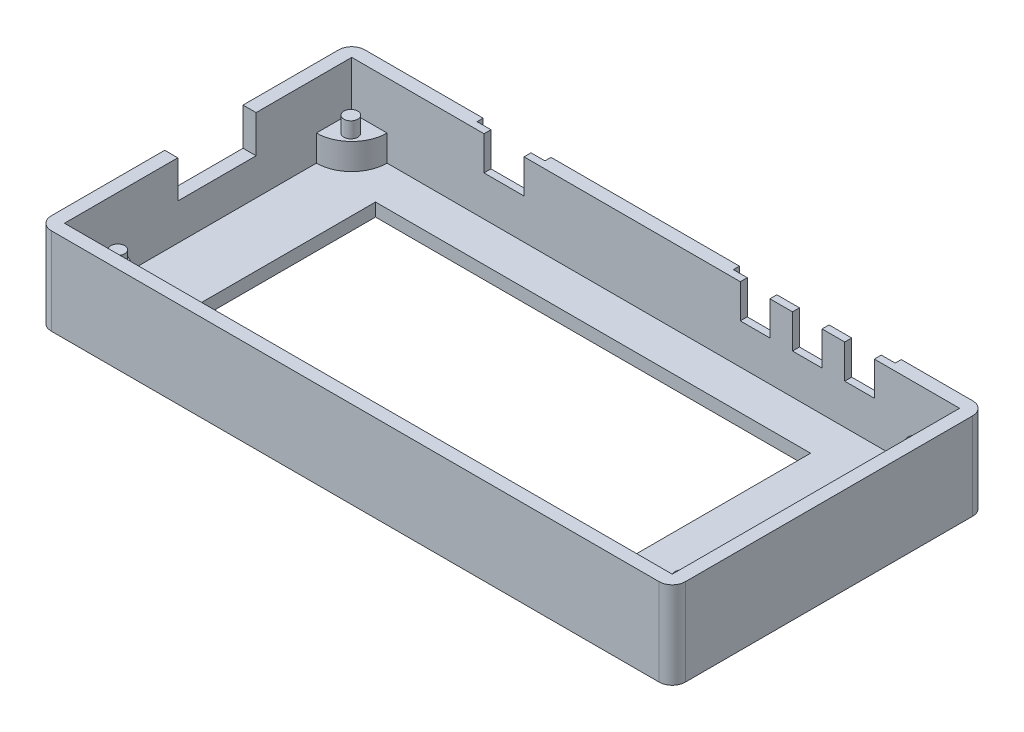
SolidWorks part; units mm, degrees
ref_plane "前视基准面" through (0, 0, 0) normal (0, 0, 1) x (1, 0, 0)
ref_plane "上视基准面" through (0, 0, 0) normal (0, 1, 0) x (1, 0, 0)
ref_plane "右视基准面" through (0, 0, 0) normal (1, 0, 0) x (0, 0, -1)
sketch "草图1" plane through (0, 0, 0) normal (0, 1, 0) x (1, 0, 0)
  line L1 (-34.9275, 15.494) -> (34.9275, 15.494)
  line L2 (-34.9275, 15.494) -> (-34.9275, -15.494)
  line L4 (34.9275, 15.494) -> (34.9275, -15.494)
  line L5 (-34.9275, 15.494) -> (34.9275, -15.494) construction
  line L6 (-34.9275, -15.494) -> (34.9275, 15.494) construction
  line L8 (-34.9275, -15.494) -> (-34.9275, -17.526)
  line L9 (-34.9275, -17.526) -> (34.9275, -17.526)
  line L10 (34.9275, -15.494) -> (34.9275, -17.526)
  line L11 (-34.9275, -15.494) -> (34.9275, -15.494)
  line L12 (-30.8635, -17.526) -> (-30.8635, 15.494) construction
  line L13 (29.7365, 15.494) -> (29.7365, -17.526) construction
  line L14 (-27.6635, 10.962) -> (-27.6635, -13.994)
  line L15 (22.3365, 10.962) -> (22.3365, -13.994)
  line L16 (0, 15.494) -> (0, -15.494) construction
  line L17 (-34.9275, 0) -> (34.9275, 0) construction
  line L18 (-27.6635, 10.962) -> (22.3365, 10.962)
  line L19 (-27.6635, -13.994) -> (22.3365, -13.994)
  arc A0 (-34.9275, -11.43) -> (-31.408, -17.526) centre (-34.9275, -15.494) cw
  arc A1 (-34.9275, 11.43) -> (-30.8635, 15.494) centre (-34.9275, 15.494) ccw
  arc A3 (34.9275, -10.43) -> (30.2891, -17.526) centre (34.9275, -15.494) ccw
  arc A4 (34.9275, 10.43) -> (29.8635, 15.494) centre (34.9275, 15.494) cw
  point P0 (0, 0)
  dimension "D4" = 4.064
  dimension "D5" = 4.064
  dimension "D6" = 5.064
  dimension "D1" = 30.988
  dimension "D2" = 69.855
  dimension "D3" = 2.032
  dimension "D7" = 5.191
  dimension "D8" = 3.2
  dimension "D9" = 7.4
  dimension "D10" = 4.532
  dimension "D11" = 3.532
extrude "凸台-拉伸1" add sketch "草图1" along normal blind 1.5 contours L8 L9 L10 L4 L1 L2
extrude "切除-拉伸2" cut sketch "草图1<6>" along normal up to next contours L14 L19 L15 L18
sketch "草图1<6>" plane through (0, 0, 0) normal (0, 1, 0) x (1, 0, 0) same geometry as "草图1"
extrude "拉伸-薄壁1" add sketch "草图1<7>" along normal blind 10 separate body thin contours L4 L10 L9 L8 L2 L1 thin type one direction wall 1.5
sketch "草图1<7>" plane through (0, 0, 0) normal (0, 1, 0) x (1, 0, 0) same geometry as "草图1"
fillet "圆角1" radius 1.5 4 edges at (36.4275, 5, -16.994) (36.4275, 5, 19.026) (-36.4275, 5, 19.026) (-36.4275, 5, -16.994)
sketch "草图2" plane through (0, 1.5, 0) normal (0, 1, 0) x (1, 0, 0)
  line L2 (-34.9275, -11.43) -> (-34.9275, -17.526)
  line L3 (-34.9275, -17.526) -> (-31.408, -17.526)
  line L4 (-30.8635, 15.494) -> (-34.9275, 15.494)
  line L5 (-34.9275, 15.494) -> (-34.9275, 11.43)
  line L7 (29.8635, 15.494) -> (34.9275, 15.494)
  line L8 (34.9275, 15.494) -> (34.9275, 10.43)
  line L9 (34.9275, -10.43) -> (34.9275, -17.526)
  line L10 (34.9275, -17.526) -> (30.2891, -17.526)
  arc A0 (29.8635, 15.494) -> (34.9275, 10.43) centre (34.9275, 15.494) ccw construction
  arc A1 (34.9275, -10.43) -> (30.2891, -17.526) centre (34.9275, -15.494) ccw construction
  arc A2 (-31.408, -17.526) -> (-34.9275, -11.43) centre (-34.9275, -15.494) ccw construction
  arc A3 (-34.9275, 11.43) -> (-30.8635, 15.494) centre (-34.9275, 15.494) ccw construction
  arc A4 (29.8635, 15.494) -> (34.9275, 10.43) centre (34.9275, 15.494) ccw
  arc A5 (34.9275, -10.43) -> (30.2891, -17.526) centre (34.9275, -15.494) ccw
  arc A6 (-31.408, -17.526) -> (-34.9275, -11.43) centre (-34.9275, -15.494) ccw
  arc A7 (-34.9275, 11.43) -> (-30.8635, 15.494) centre (-34.9275, 15.494) ccw
  line M5 (-34.9275, 15.494) -> (-34.9275, -17.526)
  line M6 (-34.9275, -17.526) -> (34.9275, -17.526)
  line M7 (34.9275, -17.526) -> (34.9275, 15.494)
  line M8 (34.9275, 15.494) -> (-34.9275, 15.494)
extrude "凸台-拉伸2" add sketch "草图2" along normal blind 3 contours A7 M5 M8 | A6 M6 M5 | A4 M8 M7 | A5 M7 M6 region at (-33.1185, 1.5, 14.7977) region at (-33.2027, 1.5, -13.7692) region at (32.6738, 1.5, 14.3906) region at (32.7783, 1.5, -13.3448)
sketch "草图3" plane through (0, 4.5, 0) normal (0, 1, 0) x (1, 0, 0)
  line L0 (34.9275, 15.494) -> (34.9275, -15.494) construction
  line L2 (34.9275, 10.43) -> (34.9275, 15.494) construction
  line L3 (-34.9275, -17.526) -> (34.9275, -17.526) construction
  line L6 (-34.9275, -15.494) -> (34.9275, -15.494) construction
  line L7 (-34.9275, 15.494) -> (-34.9275, -15.494) construction
  line L10 (0, 15.494) -> (0, -15.494) construction
  line L11 (-34.9275, 0) -> (34.9275, 0) construction
  line L12 (0, 15.494) -> (0, -15.494) construction
  line L13 (-34.9275, 0) -> (34.9275, 0) construction
  circle A2 centre (-32.9275, -13.394) radius 0.8
  circle A3 centre (-32.9275, 13.394) radius 0.8
  circle A4 centre (31.9275, -13.394) radius 0.8
  circle A5 centre (31.9275, 13.394) radius 0.8
  point P6 (-34.9275, -13.4076)
  point P7 (0, 0)
  point P12 (0, 0)
  point P26 (0, 0)
  point P27 (31.8499, -15.494)
  point P28 (0, 0)
  point P29 (0, 0)
  dimension "D2" = 0.8
  dimension "D6" = 0.8
  dimension "D1" = 2.1
  dimension "D3" = 2
  dimension "D4" = 3
  dimension "D5" = 2.1
extrude "凸台-拉伸3" add sketch "草图3" along normal blind 1.8
sketch "草图4" plane through (-34.9275, 0, 0) normal (1, 0, 0) x (0, 0, -1)
  line L0 (-11.43, 4.5) -> (11.43, 4.5) construction
  line L2 (-4.5, 10) -> (4.5, 10)
  line L3 (-4.5, 10) -> (-4.5, 5.7)
  line L4 (-4.5, 5.7) -> (4.5, 5.7)
  line L5 (4.5, 10) -> (4.5, 5.7)
  point P8 (0, 5.7)
  dimension "D1" = 1.2
  dimension "D2" = 4.3
  dimension "D3" = 9
extrude "切除-拉伸3" cut sketch "草图4" against normal up to next contours L3 L2 L5 L4
sketch "草图5" plane through (0, 0, -15.494) normal (0, 0, 1) x (1, 0, 0)
  line L0 (-30.8635, 4.5) -> (29.8635, 4.5) construction
  line L1 (15.7275, 10.1) -> (15.7275, 6.1)
  line L2 (-34.9275, 10) -> (-34.9275, 4.5) construction
  line L3 (-19.7275, 10.1) -> (-15.1275, 10.1)
  line L4 (-19.7275, 10.1) -> (-19.7275, 6.1)
  line L5 (-19.7275, 6.1) -> (-15.1275, 6.1)
  line L6 (-15.1275, 10.1) -> (-15.1275, 6.1)
  line L11 (-21.3275, 11.7) -> (-21.3275, 4.5)
  line L12 (-21.3275, 4.5) -> (-13.5275, 4.5)
  line L13 (-13.5275, 11.7) -> (-13.5275, 4.5)
  line L14 (-21.3275, 11.7) -> (-13.5275, 11.7)
  line L15 (34.9275, 10) -> (34.9275, 4.5) construction
  line L16 (21.7275, 10.1) -> (25.1275, 10.1)
  line L17 (21.7275, 10.1) -> (21.7275, 6.1)
  line L18 (21.7275, 6.1) -> (25.1275, 6.1)
  line L19 (25.1275, 10.1) -> (25.1275, 6.1)
  line L24 (8.1275, 11.7) -> (8.1275, 4.5)
  line L25 (8.1275, 4.5) -> (26.7275, 4.5)
  line L26 (26.7275, 11.7) -> (26.7275, 4.5)
  line L27 (8.1275, 11.7) -> (26.7275, 11.7)
  line L28 (15.7275, 10.1) -> (19.1275, 10.1)
  line L29 (19.1275, 10.1) -> (19.1275, 6.1)
  line L30 (15.7275, 6.1) -> (19.1275, 6.1)
  line L31 (9.7275, 10.1) -> (9.7275, 6.1)
  line L32 (9.7275, 10.1) -> (13.1275, 10.1)
  line L33 (13.1275, 10.1) -> (13.1275, 6.1)
  line L34 (9.7275, 6.1) -> (13.1275, 6.1)
  line L35 (21.7275, 10.1) -> (15.7275, 10.1) construction
  point P2 (11.4275, 6.1)
  point P10 (-17.4275, 6.1)
  point P21 (23.4275, 6.1)
  point P37 (-17.4275, 10.1)
  point P38 (-17.4275, 4.5)
  dimension "D1" = 17.5
  dimension "D2" = 4.6
  dimension "D3" = 4
  dimension "D4" = 1.6
  dimension "D6" = 3.4
  dimension "D7" = 4
  dimension "D8" = 11.5
  dimension "D9" = 1.6
  dimension "D12" = 6
  dimension "D10" = 1.6
  dimension "D13" = 1.6
  dimension "D14" = 1.6
  dimension "D15" = 1.6
  dimension "D5" = 1.6
  dimension "D11" = 3
extrude "切除-拉伸4" cut sketch "草图5" against normal up to next contours L31 L34 L33 L32 | L1 L30 L29 L28 | L19 L16 L17 L18 | L4 L3 L6 L5 region at (17.4275, 8.1, -15.494) region at (23.4275, 8.1, -15.494) region at (11.4275, 8.1, -15.494)
extrude "切除-拉伸6" cut sketch "草图5<6>" along normal blind 0.7 from surface contours L14 L13 L12 L11 | L27 L26 L25 L24 starting at face at (6.971, 7.44, -16.994)
sketch "草图5<6>" plane through (0, 0, -15.494) normal (0, 0, 1) x (1, 0, 0) same geometry as "草图5"
